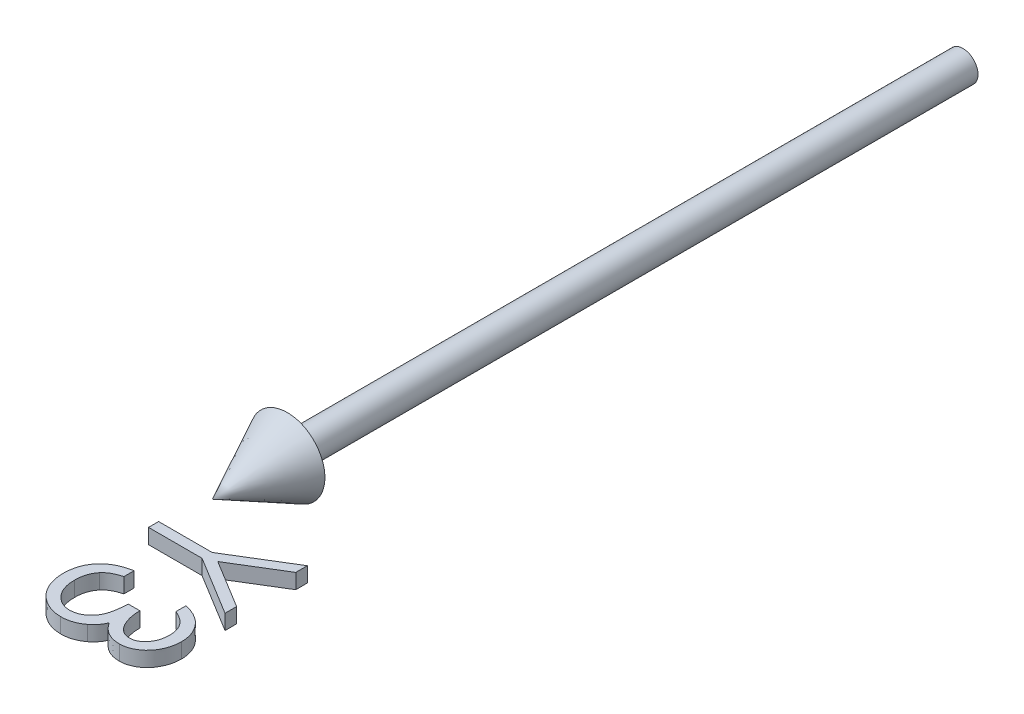
SolidWorks part; units mm, degrees
ref_plane "Front Plane" through (0, 0, 0) normal (0, 0, 1) x (1, 0, 0)
ref_plane "Top Plane" through (0, 0, 0) normal (0, 1, 0) x (1, 0, 0)
ref_plane "Right Plane" through (0, 0, 0) normal (1, 0, 0) x (0, 0, -1)
sketch "Sketch2" plane through (0, 0, 0) normal (0, 1, 0) x (1, 0, 0)
  line L0 (0, 41.95) -> (0, -114.4521) construction
  line L1 (-36.8894, 0) -> (41.4965, 0) construction
  line L2 (0, -100) -> (5, -90)
  line L3 (5, -90) -> (2, -90)
  line L4 (2, -90) -> (2, 0)
  line L5 (2, 0) -> (0, 0)
  line L6 (0, 0) -> (0, -100)
  dimension "D1" = 100
  dimension "D2" = 2
  dimension "D3" = 10
  dimension "D4" = 5
revolve "Revolve1" add sketch "Sketch2" angle 360 about L0
sketch "Sketch3" plane through (0, 0, 0) normal (0, 1, 0) x (1, 0, 0)
  line L0 (0, -101.5706) -> (0, -127.8138) construction
  text T0 "Y3\r\n" font "Century Gothic" height 15
extrude "Boss-Extrude1" add sketch "Sketch3" against normal blind 1 and the other way blind 1 separate body
equation "\"frame_arrow_length\"=100"
equation "\"D1@Sketch2\"=\"frame_arrow_length\""
equation "\"frame_arrow_odA\"=4"
equation "\"D2@Sketch2\"=\"frame_arrow_odA\"/2"
equation "\"frame_arrow_head_od\"=5"
equation "\"D4@Sketch2\"=\"frame_arrow_head_od\""
equation "\"frame_arrow_head_length\"=10"
equation "\"D3@Sketch2\"=\"frame_arrow_head_length\""
equation "\"tvarobot_theta1\"=30"
equation "\"link0_ringA_odA\"= 40"
equation "\"link0_ringA_odB\"= 25"
equation "\"link0_ringA_id\"= 20"
equation "\"link0_ringA_thickness\"= (\"link0_ringA_odB\" - \"link0_ringA_id\")/2"
equation "\"link0_ringA_height\"= 3"
equation "\"link0_ringA_heightA\"= 1.5"
equation "\"link0_ringA_heightB\"=\"link0_ringA_height\"-\"link0_ringA_heightA\""
equation "\"link0_ringB_odA\"= 40"
equation "\"link0_ringB_odB\"= 29"
equation "\"link0_ringB_id\"= \"link0_shaftA_bearing_id\"+1"
equation "\"link0_ringB_thickness\"= (\"link0_ringB_odB\" - \"link0_ringB_id\")/2"
equation "\"link0_ringB_height\"= 3"
equation "\"link0_ringB_heightA\"= 1.5"
equation "\"link0_ringB_heightB\"=\"link0_ringB_height\"-\"link0_ringB_heightA\""
equation "\"link0_shaftA_bearing_od\"=27"
equation "\"link0_shaftA_bearing_id\"=20"
equation "\"link0_shaftA_thrust_bearing_od\"=35"
equation "\"link0_shaftA_thrust_bearing_id\"=20.04"
equation "\"link0_shaftA_retaining_ring_id\"=18.5"
equation "\"link0_shaftA_retaining_ring_groove_width\"=1.5"
equation "\"link0_shaftA_spline_length\"=8.0"
equation "\"link0_shaftA_spline_depth\"=1.0"
equation "\"link0_shaftA_spline_width\"=4.0"
equation "\"link0_shaftA_odA\"=\"link0_shaftA_bearing_id\""
equation "\"link0_shaftA_odB\"=35"
equation "\"link0_shaftA_odC\"=\"link0_shaftA_bearing_id\""
equation "\"link0_shaftA_odD\"=\"link0_shaftA_odC\"-2*\"link0_shaftA_spline_depth\""
equation "\"link0_shaftA_odE\"=\"link0_shaftA_bearing_id\""
equation "\"link0_shaftA_odF\"=\"link0_shaftA_odE\"-2*\"link0_shaftA_spline_depth\""
equation "\"link0_shaftA_idA\"=10"
equation "\"link0_shaftA_idB\"=6"
equation "\"link0_shaftA_length\"=39.5"
equation "\"link0_shaftA_lengthA\"=8.0"
equation "\"link0_shaftA_lengthB\"=12.0"
equation "\"link0_shaftA_lengthC\"=35.0"
equation "\"link0_shaftA_lengthD\"=39.0"
equation "\"link0_shaftA_lengthE\"=\"link0_shaftA_length\"-\"link0_shaftA_lengthD\""
equation "\"link0_shaftA_offsetX\"=11"
equation "\"link0_shaftA_offsetY\"=0"
equation "\"link0_shaftA_bolt_pattern_dia\"=14"
equation "\"link0_motor_center_dist\"=26"
equation "\"link0_46t_pulley_spline_length\"=8"
equation "\"link0_46t_pulley_spline_depth\"=\"link0_shaftA_spline_depth\"*1.025"
equation "\"link0_46t_pulley_spline_width\"=\"link0_shaftA_spline_width\"*1.05"
equation "\"link0_46t_pulley_idA\"=\"link0_shaftA_bearing_id\"*1.025"
equation "\"link0_46t_pulley_idB\"=\"link0_46t_pulley_idA\"-2*\"link0_46t_pulley_spline_depth\""
equation "\"link0_shaftB_spline_length\"=10"
equation "\"link0_shaftB_spline_depth\"=1.0"
equation "\"link0_shaftB_spline_width\"=1.25"
equation "\"link0_shaftB_length\"=7"
equation "\"link0_shaftB_lengthA\"=1.5"
equation "\"link0_shaftB_lengthB\"=2.75"
equation "\"link0_shaftB_odA\"=32"
equation "\"link0_shaftB_odB\"=22"
equation "\"link0_shaftB_odC\"=20"
equation "\"link0_shaftB_idA\"=10"
equation "\"link0_shaftB_bolt_diameter\"=19"
equation "\"link0_shaftB_bearing_od\"=27"
equation "\"link0_shaftB_bearing_id\"=20"
equation "\"link0_motor_length\"=46.5"
equation "\"link0_motor_width\"=28.5"
equation "\"link0_motor_height\"=34"
equation "\"link0_motor_offset\"=8"
equation "\"link0_shellA_thickness\"=2.5"
equation "\"link0_shellB_thickness\"=\"link0_shellA_thickness\""
equation "\"link0_plateA_shellA_height\"=48"
equation "\"link0_shellA_width\" =\"link0_plateA_width\""
equation "\"link0_shellA_height\" = \"link0_plateA_shellA_height\"-\"link0_plateA_height\""
equation "\"link0_shellA_length\" = \"link0_plateA_lengthB\" "
equation "\"link0_shellB_length\"=\"link0_shellA_length\""
equation "\"link0_shellA_radius\" = 0.375*25.4"
equation "\"link0_shellA_radiusA\"= \"link0_plateA_radiusA\""
equation "\"link0_shellA_radiusB\"= \"link0_plateA_radiusB\""
equation "\"link0_shellA_radiusC\"= 3"
equation "\"link0_postA_height\"=7"
equation "\"link0_postA_width\"=16"
equation "\"link0_postA_length\"=20"
equation "\"link0_postA_posX\"=22"
equation "\"link0_postA_posY\"=17.5"
equation "\"link0_postA_pocket_width\"=6.0"
equation "\"link0_postA_pocket_length\"=2.5"
equation "\"link0_postA_pocket_depth\"=9"
equation "\"link0_postA_pocket_posZ\"=10"
equation "\"link0_postB_height\"=7"
equation "\"link0_postB_width\"=16"
equation "\"link0_postB_length\"=20"
equation "\"link0_postB_posX\"=22"
equation "\"link0_postB_posY\"=17.5"
equation "\"link0_postB_id\"=3.0"
equation "\"link0_postB_pocket_width\"=6.0"
equation "\"link0_postB_pocket_length\"=2.5"
equation "\"link0_postB_pocket_depth\"=9"
equation "\"link0_postB_pocket_posZ\"=10"
equation "\"link0_postC_height\"=7"
equation "\"link0_postC_width\"=16"
equation "\"link0_postC_length\"=20"
equation "\"link0_postC_posX\"=22"
equation "\"link0_postC_posY\"=17.5"
equation "\"link0_postC_id\"=3.0"
equation "\"link0_postC_pocket_width\"=6.0"
equation "\"link0_postC_pocket_length\"=2.5"
equation "\"link0_postC_pocket_depth\"=9"
equation "\"link0_postC_pocket_posZ\"=10"
equation "\"link0_postD_height\"=7"
equation "\"link0_postD_width\"=16"
equation "\"link0_postD_length\"=20"
equation "\"link0_postD_posX\"=22"
equation "\"link0_postD_posY\"=17.5"
equation "\"link0_postD_id\"=3.0"
equation "\"link0_postD_pocket_width\"=6.0"
equation "\"link0_postD_pocket_length\"=3.0"
equation "\"link0_postD_pocket_depth\"=9"
equation "\"link0_postD_pocket_posZ\"=10"
equation "\"link0_postE_height\"=5"
equation "\"link0_postE_width\"=16"
equation "\"link0_postE_length\"=\"link0_plateE_lengthA\"-\"link0_lip_height\""
equation "\"link0_postE_posZ\"=22"
equation "\"link0_postE_posX\"=17.5"
equation "\"link0_postE_posY\"=22"
equation "\"link0_postE_id\"=3.0"
equation "\"link0_postE_cbore_id\"=6.5"
equation "\"link0_postE_hole_id\"=3"
equation "\"link0_postF_posZ\"=22"
equation "\"link0_postF_posX\"=17.5"
equation "\"link0_postF_posY\"=\"link0_plateB_lengthA\"+4"
equation "\"link0_postF_id\"=3.0"
equation "\"link0_postF_cbore_id\"=6.5"
equation "\"link0_postF_hole_id\"=3"
equation "\"link0_postG_posZ\"=22"
equation "\"link0_postG_posX\"=17.5"
equation "\"link0_postG_posY\"=\"link0_plateB_lengthA\"+12"
equation "\"link0_postG_id\"=3.0"
equation "\"link0_postG_cbore_id\"=6.5"
equation "\"link0_postG_hole_id\"=3"
equation "\"link0_postHIJ_posY\"=6"
equation "\"link0_postH_posX\"=28"
equation "\"link0_postH_posY\"=20"
equation "\"link0_postH_posZ\"=20"
equation "\"link0_postH_length\"=10"
equation "\"link0_postI_posX\"=28"
equation "\"link0_postI_posY\"=20"
equation "\"link0_postI_posZ\"=135"
equation "\"link0_postI_length\"=10"
equation "\"link0_postJ_posX\"=28"
equation "\"link0_postJ_posY\"=20"
equation "\"link0_postJ_posZ\"=175"
equation "\"link0_postJ_length\"=10"
equation "\"link0_postK_posX\"=28"
equation "\"link0_postK_posY\"=20"
equation "\"link0_postK_posZ\"=175"
equation "\"link0_postK_length\"=10"
equation "\"link0_postL_posX\"=28"
equation "\"link0_postL_posY\"=20"
equation "\"link0_postL_posZ\"=135"
equation "\"link0_postL_length\"=10"
equation "\"link0_postM_posX\"=28"
equation "\"link0_postM_posY\"=20"
equation "\"link0_postM_posZ\"=35"
equation "\"link0_postM_length\"=10"
equation "\"link0_plateA_lengthA\"=30"
equation "\"link0_plateA_lengthB\"=150"
equation "\"link0_plateA_lengthC\"=30"
equation "\"link0_plateA_length\"=\"link0_plateA_lengthA\"+\"link0_plateA_lengthB\"+\"link0_plateA_lengthC\""
equation "\"link0_plateA_width\"=  68"
equation "\"link0_plateA_height\"= \"link0_plateA_radiusA\""
equation "\"link0_plateA_thickness\"=\"link0_shellA_thickness\""
equation "\"link0_plateA_radius\"= 9.5"
equation "\"link0_plateA_radiusA\"= 18"
equation "\"link0_plateA_radiusB\"= 18"
equation "\"link0_plateA_radiusC\"= 3"
equation "\"link0_plateB_length\"= 40"
equation "\"link0_plateB_width\"= \"link0_plateA_width\"*1.005"
equation "\"link0_plateB_height\"= \"link0_plateA_shellA_height\"*1.005"
equation "\"link0_plateB_lengthA\"=\"link0_lip_height\"+\"link0_plateD_thickness\"+\"link0_motor_mount_thickness\""
equation "\"link0_plateB_lengthB\"=\"link0_plateB_height\"-\"link0_plateB_lengthA\""
equation "\"link0_plateB_radiusA\"= \"link0_plateA_radiusA\""
equation "\"link0_plateB_radiusB\"= \"link0_plateA_radiusB\""
equation "\"link0_plateB_radiusC\"= 3"
equation "\"link0_plateB_idA\"=\"link0_shaftA_odC\"+1"
equation "\"link0_plateB_idB\"=\"link0_shaftA_bearing_od\"-2"
equation "\"link0_plateB_idC\"=\"link0_shaftA_bearing_od\"*1.005"
equation "\"link0_plateB_idD\"=\"link0_shaftA_thrust_bearing_od\"+1 "
equation "\"link0_plateB_depthA\"=1.0"
equation "\"link0_plateB_depthB\"=2.0"
equation "\"link0_plateB_depthC\"=8"
equation "\"link0_plateB_depthD\"=\"link0_plateB_length\"-\"link0_lip_height\"-\"link0_plateD_thickness\" "
equation "\"link0_plateC_length\"=\"link0_plateB_length\""
equation "\"link0_plateC_width\"= \"link0_plateB_width\""
equation "\"link0_plateC_height\"= .1*25.4"
equation "\"link0_plateA_hole_od\" = 0.1*25.4"
equation "\"link0_plateA_hole_delx\" = 0.5*25.4"
equation "\"link0_plateA_hole_delz\" = 0.75*25.4"
equation "\"link0_plateA_hole_offx\" = 0.0*25.4"
equation "\"link0_plateA_hole_offz\" = \"link0_plateA_length\"/2"
equation "\"link0_plateB_hole_od\" = 0.1*25.4"
equation "\"link0_plateB_hole_delx\"= 0.75*25.4"
equation "\"link0_plateB_hole_delz\"= 0.75*25.4"
equation "\"link0_plateB_hole_offx\"= 0.0*25.4"
equation "\"link0_plateB_hole_offz\"= 0.0*25.4"
equation "\"link0_plateC_hole_od\"= 0.1*25.4"
equation "\"link0_plateC_hole_delx\"= 0.75*25.4"
equation "\"link0_plateC_hole_delz\"= 0.75*25.4"
equation "\"link0_plateC_hole_offx\"= 0.0*25.4"
equation "\"link0_plateC_hole_offz\"= 0.0*25.4"
equation "\"link0_plateD_height\"=\"link0_plateB_height\"-2*\"link0_shellA_thickness\""
equation "\"link0_plateD_width\"=\"link0_plateB_width\"-2*\"link0_shellA_thickness\""
equation "\"link0_plateD_thickness\"=10"
equation "\"link0_plateD_radiusA\"=\"link0_plateB_radiusA\"-\"link0_shellA_thickness\""
equation "\"link0_plateD_odA\"= .375*25.4"
equation "\"link0_plateD_odB\"= .375*25.4"
equation "\"link0_plateD_bearing_id\"=20"
equation "\"link0_plateD_bearing_od\"=27"
equation "\"link0_plateE_radiusA\"=\"link0_plateA_radiusA\""
equation "\"link0_plateE_radiusB\"=\"link0_plateA_radiusB\""
equation "\"link0_plateE_radiusC\"=8.0"
equation "\"link0_plateE_length\"=30"
equation "\"link0_plateE_lengthA\"=16"
equation "\"link0_plateE_height\"=\"link0_plateB_height\""
equation "\"link0_plateE_width\"=\"link0_plateB_width\""
equation "\"link0_plateE_odA\"=\"gantry_coupler_id\"*0.99"
equation "\"link0_plateE_idA\"=\"link0_plateE_odA\"-20.0"
equation "\"link0_plateE_spline_depth\"=\"link0_poleA_spline_depth\"*1.05"
equation "\"link0_plateE_spline_width\"=\"link0_poleA_spline_width\"*1.075"
equation "\"link0_plateE_spline_length\"=\"link0_poleA_spline_length\""
equation "\"link0_plateE_coupler_length\"=46"
equation "\"link0_lip_height\"=5.0"
equation "\"link0_lip_thickness\"=2.0"
equation "\"link0_motor_mount_thickness\"=8.0"
equation "\"link0_motor_mount_idA\"=22"
equation "\"link0_motor_mount_idB\"=\"link0_shaftB_bearing_od\"*1.005"
equation "\"link0_motor_mount_idC\"=\"link0_shaftB_bearing_od\"-2"
equation "\"link0_motor_mount_depthA\"=5.5"
equation "\"link0_motor_mount_height\"=\"link0_plateD_height\""
equation "\"link0_motor_mount_width\"=\"link0_plateD_width\""
equation "\"link0_motor_mountL_height\"=36"
equation "\"link0_motor_mountL_heightA\"=12"
equation "\"link0_motor_mountL_length\"=50"
equation "\"link0_motor_mountL_lengthA\"=36"
equation "\"gantry_coupler_od\"=25.4*2.0"
equation "\"gantry_coupler_id\"=1.645*25.4"
equation "\"gantry_coupler_offsetX\"=\"link0_plateE_width\"/2"
equation "\"link0_poleA_odA\"=20"
equation "\"link0_poleA_odB\"=36"
equation "\"link0_poleA_idA\"=\"link0_poleA_odA\"-2*\"link0_poleA_thickness\""
equation "\"link0_poleA_idB\"=(\"link0_plateE_idA\"/2+1.5*\"link0_lip_thickness\")*1.04"
equation "\"link0_poleA_thickness\"=3.5"
equation "\"link0_poleA_length\"=100"
equation "\"link0_poleA_lengthA\"=18.5"
equation "\"link0_poleA_lengthB\"=80"
equation "\"link0_poleA_gasket_thickness\"=1.5"
equation "\"link0_poleA_spline_depth\"=1.0"
equation "\"link0_poleA_spline_width\"=4.0"
equation "\"link0_poleA_spline_length\"=10.0"
equation "\"link1_plateB_length\"=30"
equation "\"link1_lip_height\"=\"link0_lip_height\""
equation "\"link0_tension_plateA_width\"=12"
equation "\"link0_tension_plateA_lengthA\"=10.5"
equation "\"link0_tension_plateB_width\"=\"link0_tension_plateA_width\""
equation "\"link0_tension_plateB_lengthA\"=\"link0_tension_plateA_lengthA\""
equation "\"link0_tension_wheelA_posZ\"=7"
equation "\"link0_tension_wheelA_posX\"=\"link0_plateD_height\"/2-\"link0_tension_plateA_lengthA\""
equation "\"link0_m2_clear_hole_id\"=2.35"
equation "\"link0_m2_insert_hole_id\"=2.5"
equation "\"link0_m2_tap_hole_id\"=1.75"
equation "\"link0_m2_nut_socket_width\"=4.25"
equation "\"link0_m2_nut_socket_depth\"=2.5"
equation "\"link0_m2_cbore_id\"=3.75"
equation "\"link0_m2_cbore_depth\"=7"
equation "\"link0_m2_5_clear_hole_id\"=2.75"
equation "\"link0_m2_5_insert_hole_id\"=2.75"
equation "\"link0_m2_5_tap_hole_id\"=2.25"
equation "\"link0_m2_5_nut_socket_width\"=5.25"
equation "\"link0_m2_5_nut_socket_depth\"=2.5"
equation "\"link0_m2_5_cbore_id\"=4.75"
equation "\"link0_m2_5_cbore_depth\"=2.5"
equation "\"link0_m2_5_insert_access_length\"=6.0"
equation "\"link0_m2_5_insert_access_width\"=3.0"
equation "\"link0_m3_clear_hole_id\"=3.25"
equation "\"link0_m3_insert_hole_id\"=3"
equation "\"link0_m3_tap_hole_id\"=2.75"
equation "\"link0_m3_nut_socket_width\"=5.75"
equation "\"link0_m3_nut_socket_depth\"=4.0"
equation "\"link0_m3_cbore_id\"=5.75"
equation "\"link0_m3_cbore_depth\"=3.5"
equation "\"link0_m3_insert_access_length\"=4.5"
equation "\"link0_m3_insert_access_width\"=3.5"
equation "\"link0_rpi_mount_height\"=6"
equation "\"link0_rpi_mount_width\"=49"
equation "\"link0_rpi_mount_length\"=58"
equation "\"link0_rpi_mount_post_od\"=6"
equation "\"link0_rpi_mount_posZ\"=72"
equation "\"link0_rpi_mount_posX\"=11.5"
equation "\"link0_mcu_mount_height\"=5"
equation "\"link0_mcu_mount_width\"=49"
equation "\"link0_mcu_mount_length\"=58"
equation "\"link0_mcu_mount_post_od\"=6"
equation "\"link0_mcu_mount_posZ\"=164"
equation "\"link0_mcu_mount_posX\"=4"
equation "\"link0_pwr_mount_height\"=4"
equation "\"link0_pwr_mount_width\"=15.75"
equation "\"link0_pwr_mount_length\"=75.75"
equation "\"link0_pwr_mount_post_od\"=6"
equation "\"link0_pwr_mount_posZ\"=75"
equation "\"link0_pwr_mount_posX\"=16"
equation "\"link0_pwr_board_height\"=6"
equation "\"link0_pwr_board_width\"=21"
equation "\"link0_pwr_board_length\"=80"
